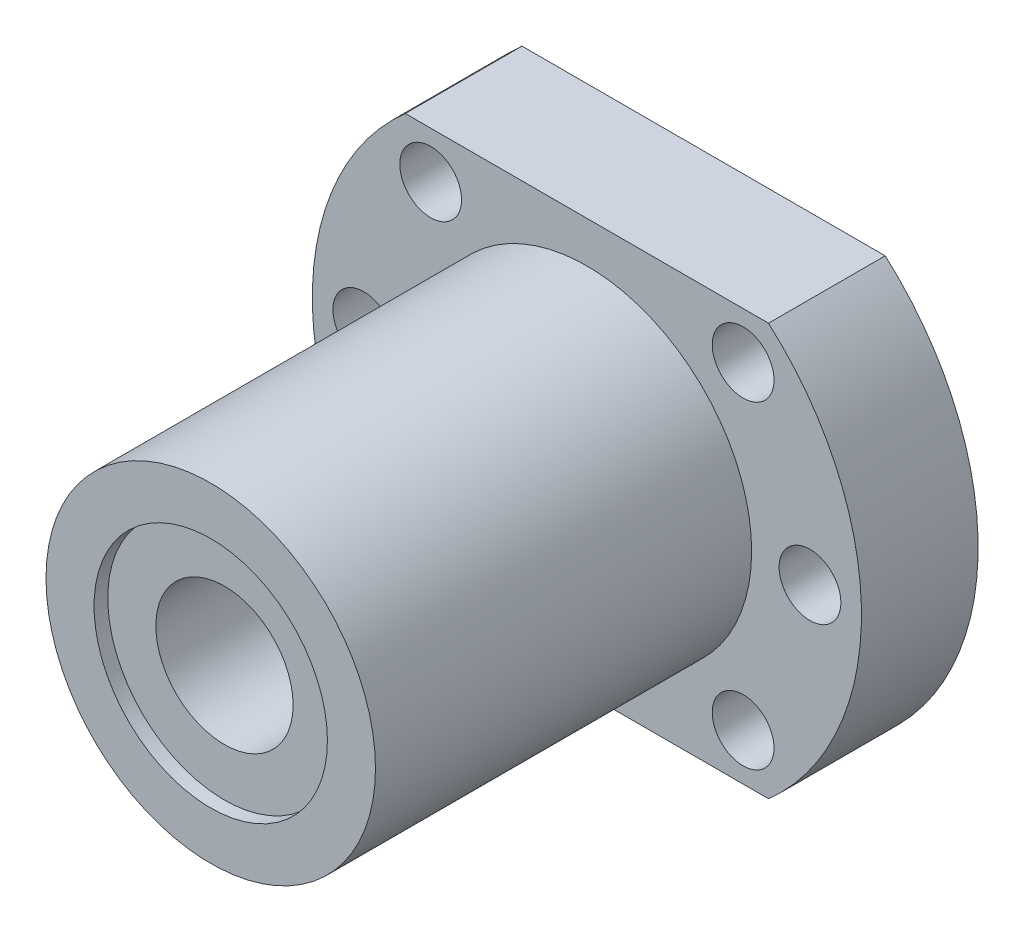
SolidWorks part; units mm, degrees
ref_plane "Alzado" through (0, 0, 0) normal (0, 0, 1) x (1, 0, 0)
ref_plane "Planta" through (0, 0, 0) normal (0, 1, 0) x (1, 0, 0)
ref_plane "Vista lateral" through (0, 0, 0) normal (1, 0, 0) x (0, 0, -1)
sketch "Croquis1" plane through (0, 0, 0) normal (0, 0, 1) x (1, 0, 0)
  line L0 (-13.2288, 15) -> (13.2288, 15)
  line L1 (-13.2288, -15) -> (13.2288, -15)
  circle A0 centre (0, 0) radius 20 construction
  arc A1 (-13.2288, 15) -> (-13.2288, -15) centre (0, 0) ccw
  arc A2 (13.2288, 15) -> (13.2288, -15) centre (0, 0) cw
  dimension "D1" = 40
  dimension "D2" = 15
  dimension "D3" = 15
extrude "Saliente-Extruir1" add sketch "Croquis1" along normal blind 8.5
sketch "Croquis2" plane through (0, 0, 8.5) normal (0, 0, 1) x (1, 0, 0)
  circle A0 centre (0, 0) radius 12
  dimension "D1" = 24
extrude "Saliente-Extruir2" add sketch "Croquis2" along normal blind 27.4
sketch "Croquis3" plane through (0, 0, 35.9) normal (0, 0, 1) x (1, 0, 0)
  circle A0 centre (0, 0) radius 5
  dimension "D1" = 10
extrude "Cortar-Extruir1" cut sketch "Croquis3" against normal up to surface (35.9 mm away) up to face at (0, 0, 0)
sketch "Croquis4" plane through (0, 0, 35.9) normal (0, 0, 1) x (1, 0, 0)
  circle A0 centre (0, 0) radius 8.5
  dimension "D1" = 17
extrude "Cortar-Extruir2" cut sketch "Croquis4" against normal blind 1
sketch "Croquis5" plane through (0, 0, 0) normal (0, 0, -1) x (-1, 0, 0)
  circle A0 centre (0, 0) radius 8.5
  dimension "D1" = 17
extrude "Cortar-Extruir3" cut sketch "Croquis5" against normal blind 1
sketch "Croquis6" plane through (0, 0, 0) normal (0, 0, -1) x (-1, 0, 0)
  line L0 (-16.25, 0) -> (16.25, 0) construction
  line L1 (0, 0) -> (11.3799, 11.6) construction
  line L2 (0, 0) -> (11.3799, -11.6) construction
  line L3 (0, 0) -> (0, 16.25) construction
  circle A0 centre (0, 0) radius 16.25 construction
  circle A1 centre (11.3799, -11.6) radius 2.25
  circle A2 centre (16.25, 0) radius 2.25
  circle A3 centre (11.3799, 11.6) radius 2.25
  circle A4 centre (-11.3799, -11.6) radius 2.25
  circle A5 centre (-16.25, 0) radius 2.25
  circle A6 centre (-11.3799, 11.6) radius 2.25
  point P6 (0, 0)
  dimension "D1" = 32.5
  dimension "D4" = 4.5
  dimension "D2" = 11.6
  dimension "D3" = 11.6
extrude "Cortar-Extruir4" cut sketch "Croquis6" against normal up to surface (8.5 mm away) up to face at (12, 0, 8.5)
equation "\"D3@Croquis6\"=\"D2@Croquis6\""
